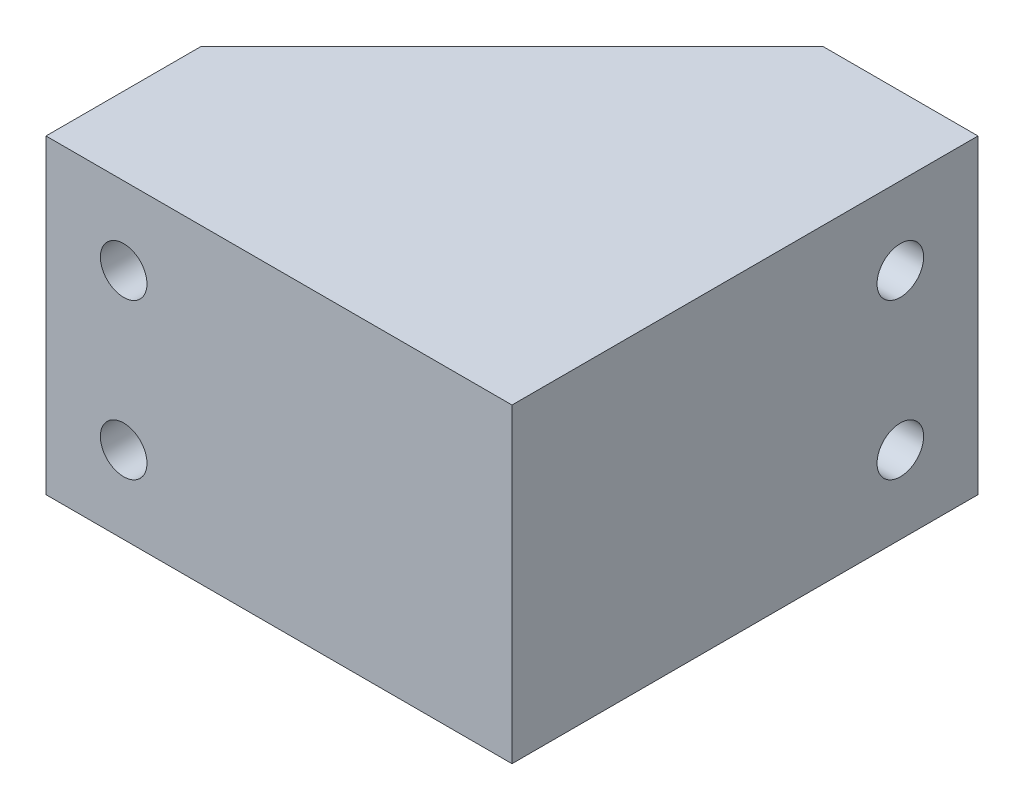
SolidWorks part; units mm, degrees
ref_plane "Front Plane" through (0, 0, 0) normal (0, 0, 1) x (1, 0, 0)
ref_plane "Top Plane" through (0, 0, 0) normal (0, 1, 0) x (1, 0, 0)
ref_plane "Right Plane" through (0, 0, 0) normal (1, 0, 0) x (0, 0, -1)
sketch "Sketch1" plane through (0, 0, 0) normal (0, 1, 0) x (1, 0, 0)
  line L0 (-9.5478, -2.6496) -> (3.1522, 10.0504)
  line L1 (9.5022, 10.0504) -> (9.5022, -8.9996)
  line L2 (9.5022, -8.9996) -> (-9.5478, -8.9996)
  line L3 (-9.5478, -8.9996) -> (-9.5478, -2.6496)
  line L4 (3.1522, 10.0504) -> (9.5022, 10.0504)
  line L5 (-15.8978, -8.9996) -> (-9.5478, -2.6496) construction
  line L6 (-9.5478, -8.9996) -> (-15.8978, -8.9996) construction
  line L7 (3.1522, 10.0504) -> (9.5022, 16.4004) construction
  line L8 (9.5022, 16.4004) -> (9.5022, 10.0504) construction
  dimension "D1" = 25.4
  dimension "D2" = 25.4
  dimension "D3" = 19.05
  dimension "D4" = 19.05
extrude "Boss-Extrude1" add sketch "Sketch1" along normal mid plane 12.7
sketch "Sketch2" plane through (9.5022, 0, 0) normal (1, 0, 0) x (0, 0, -1)
  line L0 (-8.9996, 0) -> (10.0504, 0) construction
  line L1 (-8.9996, 6.35) -> (-8.9996, -6.35) construction
  line L2 (10.0504, 6.35) -> (10.0504, -6.35) construction
  circle A0 centre (6.8754, 3.175) radius 0.9525
  circle A1 centre (6.8754, -3.175) radius 0.9525
  point P7 (0, 0)
  point P10 (0, 0)
  dimension "D1" = 1.905
  dimension "D2" = 6.35
  dimension "D3" = 15.875
extrude "Cut-Extrude1" cut sketch "Sketch2" against normal through all
sketch "Sketch3" plane through (0, 0, 8.9996) normal (0, 0, 1) x (1, 0, 0)
  line L0 (-9.5478, 0) -> (9.5022, 0) construction
  line L1 (-9.5478, 6.35) -> (-9.5478, -6.35) construction
  line L2 (9.5022, 6.35) -> (9.5022, -6.35) construction
  circle A0 centre (-6.3728, 3.175) radius 0.9525
  circle A1 centre (-6.3728, -3.175) radius 0.9525
  dimension "D1" = 1.905
  dimension "D2" = 6.35
  dimension "D3" = 15.875
extrude "Cut-Extrude2" cut sketch "Sketch3" against normal through all
